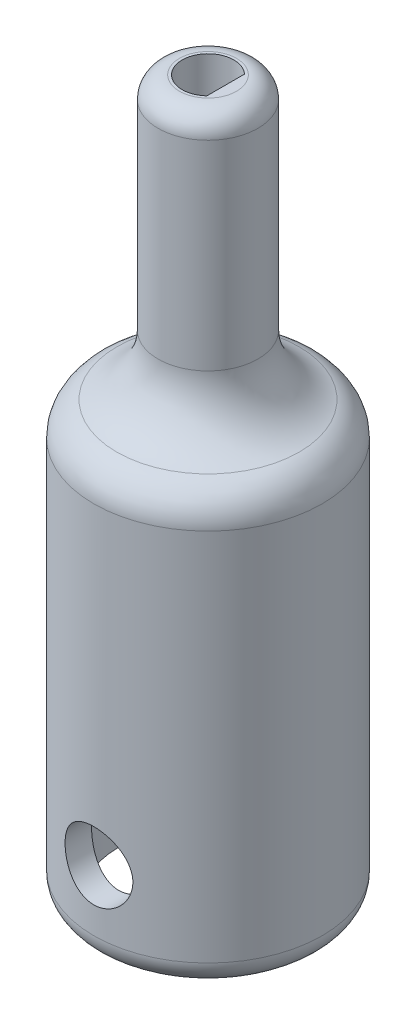
SolidWorks part; units mm, degrees
ref_plane "Front Plane" through (0, 0, 0) normal (0, 0, 1) x (1, 0, 0)
ref_plane "Top Plane" through (0, 0, 0) normal (0, 1, 0) x (1, 0, 0)
ref_plane "Right Plane" through (0, 0, 0) normal (1, 0, 0) x (0, 0, -1)
sketch "Sketch1" plane through (0, 0, 0) normal (1, 0, 0) x (0, 0, -1)
  line L0 (0, 0) -> (-16, 0)
  line L2 (-16, 0) -> (-16, 60)
  line L3 (-7, 80) -> (-7, 100)
  line L4 (-7, 100) -> (0, 100)
  line L6 (-7, 80) -> (-7, 69)
  line L8 (0, 2.4115) -> (0, 50002.4115) construction
  line L9 (0, 0) -> (0, 100)
  arc A0 (-7, 69) -> (-16, 60) centre (-16, 69) cw
  dimension "D4" = 9
  dimension "D1" = 60
  dimension "D2" = 20
  dimension "D3" = 9
  dimension "D5" = 20
  dimension "D6" = 16
revolve "Revolve1" add sketch "Sketch1" angle 360 about L8 other way angle 360
sketch "Sketch2" plane through (0, 0, 0) normal (0, 0, 1) x (1, 0, 0)
  line L0 (-16, 0) -> (16, 0) construction
  line L1 (16, 0) -> (16, 60) construction
  circle A0 centre (0, 12) radius 4.75
  dimension "D1" = 9.5
  dimension "D2" = 12
  dimension "D3" = 16
extrude "Cut-Extrude1" cut sketch "Sketch2" against normal through all both and the other way through all
sketch "Sketch3" plane through (0, 0, 0) normal (0, -1, 0) x (1, 0, 0)
  circle A0 centre (0, 0) radius 12.5
  dimension "D1" = 25
extrude "Cut-Extrude2" cut sketch "Sketch3" against normal blind 53
sketch "Sketch4" plane through (0, 100, 0) normal (0, 1, 0) x (1, 0, 0)
  line L0 (0, 3.6195) -> (0, -3.6195) construction
  line L5 (3.6195, 0) -> (-3.6195, 0) construction
  line L6 (2.4765, 2.6396) -> (2.4765, -2.6396)
  circle A0 centre (0, 0) radius 3.6195
  point P9 (0, 0)
  point P12 (0, 0)
  dimension "D1" = 7.239
  dimension "D2" = 1.143
extrude "Cut-Extrude3" cut sketch "Sketch4" against normal blind 43 contours A0 region at (-0.3315, 100, 0)
fillet "Fillet1" radius 5 1 edges at (0, 60, -16) tangent propagation no
fillet "Fillet2" radius 3 1 edges at (0, 100, -7)
fillet "Fillet3" radius 3.5 1 edges at (0, 0, -16)
